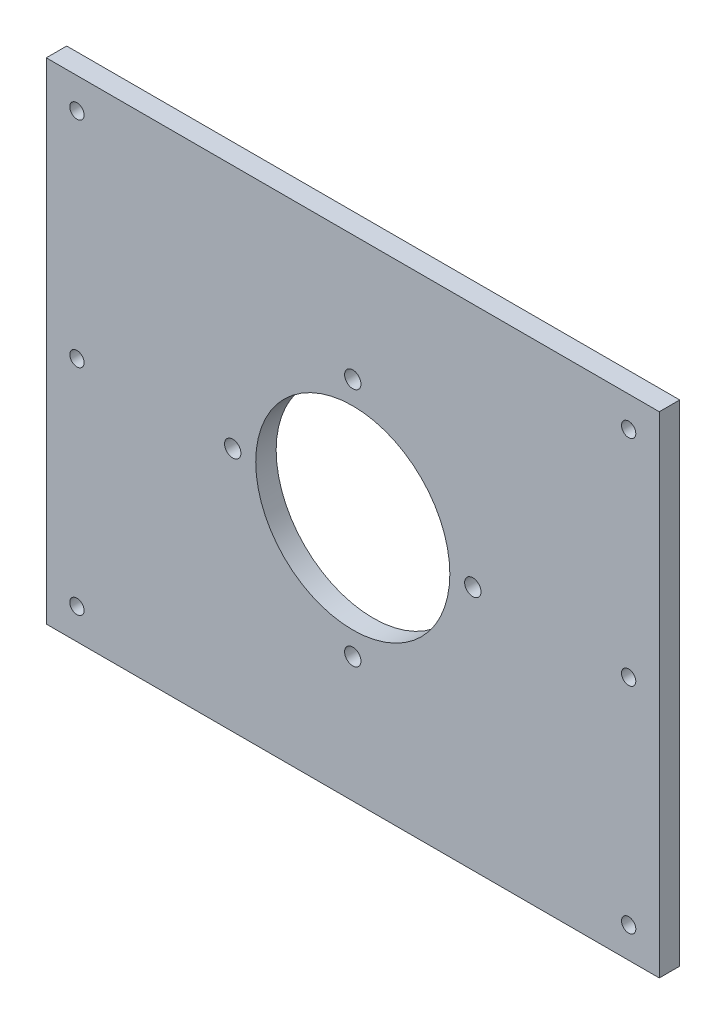
SolidWorks part; units mm, degrees
ref_plane "Front Plane" through (0, 0, 0) normal (0, 0, 1) x (1, 0, 0)
ref_plane "Top Plane" through (0, 0, 0) normal (0, 1, 0) x (1, 0, 0)
ref_plane "Right Plane" through (0, 0, 0) normal (1, 0, 0) x (0, 0, -1)
sketch "Sketch1" plane through (0, 0, 0) normal (0, 0, 1) x (1, 0, 0)
  line L1 (-168.5483, -132.9715) -> (212.4517, -132.9715)
  line L2 (-168.5483, -132.9715) -> (-168.5483, 171.8285)
  line L3 (-168.5483, 171.8285) -> (212.4517, 171.8285)
  line L4 (212.4517, -132.9715) -> (212.4517, 171.8285)
  dimension "D1" = 381
  dimension "D2" = 304.8
extrude "Boss-Extrude1" add sketch "Sketch1" along normal blind 12.7
sketch "Sketch2" plane through (0, 0, 0) normal (0, 0, -1) x (-1, 0, 0)
  line L3 (-212.4517, 171.8285) -> (168.5483, 171.8285) construction
  line L5 (168.5483, 171.8285) -> (168.5483, -132.9715) construction
  line L7 (-21.9517, 19.4285) -> (-96.5517, 19.4285)
  line L8 (-21.9517, 19.4285) -> (-21.9517, -55.1715)
  line L9 (-21.9517, 19.4285) -> (52.6483, 19.4285)
  line L10 (-212.4517, -132.9715) -> (-212.4517, 171.8285) construction
  line L11 (168.5483, -132.9715) -> (-212.4517, -132.9715) construction
  circle A0 centre (-21.9517, 19.4285) radius 74.6
  circle A2 centre (-21.9517, 94.0285) radius 5.08
  circle A3 centre (-96.5517, 19.4285) radius 5.08
  circle A4 centre (52.6483, 19.4285) radius 5.08
  circle A5 centre (-21.9517, -55.1715) radius 5.08
  circle A6 centre (-21.9517, 19.4285) radius 60.325
  circle A7 centre (-193.4017, 152.7785) radius 4.445
  circle A8 centre (-193.4017, -113.9215) radius 4.445
  circle A9 centre (149.4983, -113.9215) radius 4.445
  circle A10 centre (149.4983, 152.7785) radius 4.445
  circle A11 centre (-193.4017, 19.4285) radius 4.445
  circle A12 centre (149.4983, 19.4285) radius 4.445
  dimension "D1" = 149.2
  dimension "D4" = 10.16
  dimension "D5" = 10.16
  dimension "D6" = 10.16
  dimension "D7" = 10.16
  dimension "D8" = 120.65
  dimension "D9" = 8.89
  dimension "D12" = 8.89
  dimension "D15" = 8.89
  dimension "D18" = 8.89
  dimension "D21" = 8.89
  dimension "D24" = 8.89
  dimension "D2" = 152.4
  dimension "D3" = 190.5
  dimension "D10" = 19.05
  dimension "D11" = 19.05
  dimension "D13" = 19.05
  dimension "D14" = 19.05
  dimension "D16" = 19.05
  dimension "D17" = 19.05
  dimension "D19" = 19.05
  dimension "D20" = 19.05
  dimension "D22" = 19.05
  dimension "D23" = 152.4
  dimension "D25" = 19.05
  dimension "D26" = 152.4
extrude "Cut-Extrude1" cut sketch "Sketch2" along normal blind 94.996 and the other way blind 157.226 contours A0 A2 | A0 A2 | L9 A6 L7 | L8 A6 L9 | L7 A6 L8 | A0 A4 | L9 A4 A0 | A0 A5 L8 | L8 A5 A0 | A0 A5 | A0 A3 | L7 A3 A0 | A0 A3 L7 | A12 | A9 | A7 | A8 | A4 | A10 | A11 region at (94.3648, 17.2967, 0) region at (94.3648, 21.5602, 0) region at (98.6762, 19.4285, 0) region at (21.9517, 45.0312, 0) region at (47.5544, -6.1742, 0) region at (-3.6511, -6.1742, 0) region at (21.9517, 96.153, 0) region at (21.9517, 91.8416, 0) region at (24.0834, -52.9846, 0) region at (21.9517, -57.2961, 0) region at (-50.4615, 17.2967, 0) region at (19.8199, -52.9846, 0) region at (-54.7729, 19.4285, 0) region at (193.4017, 152.7785, 0) region at (193.4017, -113.9215, 0) region at (-149.4983, -113.9215, 0) region at (-149.4983, 19.4285, 0)
